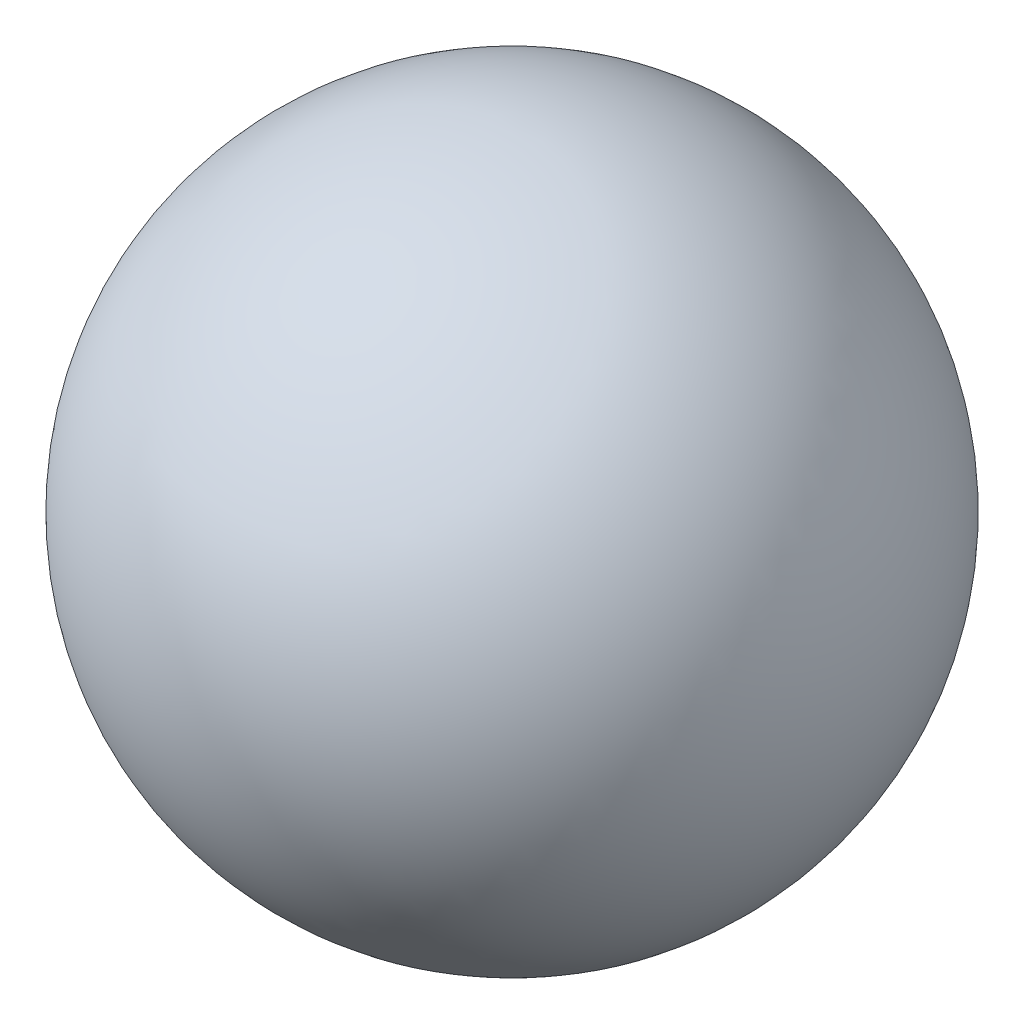
SolidWorks part; units mm, degrees
ref_plane "前视基准面" through (0, 0, 0) normal (0, 0, 1) x (1, 0, 0)
ref_plane "上视基准面" through (0, 0, 0) normal (0, 1, 0) x (1, 0, 0)
ref_plane "右视基准面" through (0, 0, 0) normal (1, 0, 0) x (0, 0, -1)
sketch "草图1" plane through (0, 0, 0) normal (0, 0, 1) x (1, 0, 0)
  line L0 (0, 17.311) -> (0, -16.7431) construction
  line L1 (0, 50) -> (0, -50)
  arc A0 (0, -50) -> (0, 50) centre (0, 0) ccw
  dimension "D1" = 100
revolve "旋转3" add sketch "草图1" angle 360 about L0
